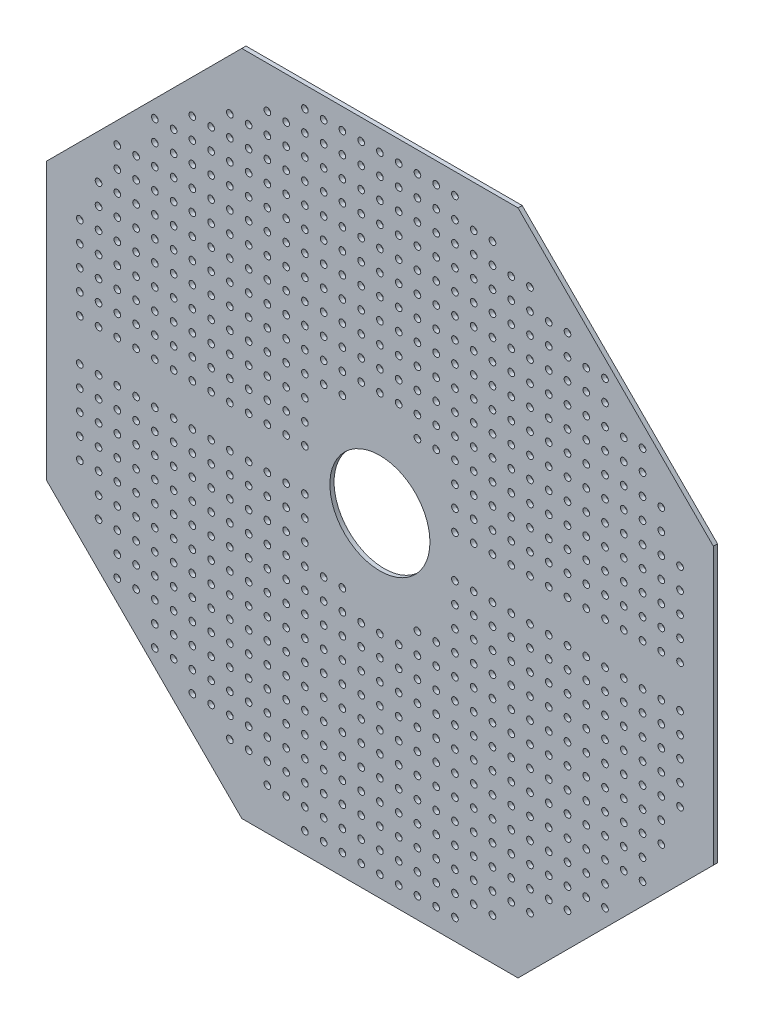
SolidWorks part; units mm, degrees
ref_plane "前视基准面" through (0, 0, 0) normal (0, 0, 1) x (1, 0, 0)
ref_plane "上视基准面" through (0, 0, 0) normal (0, 1, 0) x (1, 0, 0)
ref_plane "右视基准面" through (0, 0, 0) normal (1, 0, 0) x (0, 0, -1)
other "Configuration Table"
sketch "草图1" plane through (0, 0, 0) normal (0, 0, 1) x (1, 0, 0)
  line L0 (-1242.6073, 0) -> (1242.6073, 0) construction
  line L2 (0, -846.9805) -> (0, 846.9805) construction
  line L5 (331.3708, 800) -> (-331.3708, 800)
  line L6 (-331.3708, 800) -> (-800, 331.3708)
  line L7 (-800, 331.3708) -> (-800, -331.3708)
  line L8 (-800, -331.3708) -> (-331.3708, -800)
  line L9 (-331.3708, -800) -> (331.3708, -800)
  line L10 (331.3708, -800) -> (800, -331.3708)
  line L11 (800, -331.3708) -> (800, 331.3708)
  line L12 (800, 331.3708) -> (331.3708, 800)
  circle A2 centre (0, 0) radius 120
  circle A502 centre (0, 0) radius 800 construction
  circle A582 centre (180, 50) radius 8
  circle A583 centre (225, 50) radius 8
  circle A584 centre (270, 50) radius 8
  circle A585 centre (315, 50) radius 8
  circle A586 centre (360, 50) radius 8
  circle A587 centre (405, 50) radius 8
  circle A588 centre (450, 50) radius 8
  circle A589 centre (495, 50) radius 8
  circle A590 centre (540, 50) radius 8
  circle A591 centre (585, 50) radius 8
  circle A592 centre (630, 50) radius 8
  circle A593 centre (675, 50) radius 8
  circle A594 centre (720, 50) radius 8
  circle A599 centre (180, 100) radius 8
  circle A600 centre (225, 100) radius 8
  circle A601 centre (270, 100) radius 8
  circle A602 centre (315, 100) radius 8
  circle A603 centre (360, 100) radius 8
  circle A604 centre (405, 100) radius 8
  circle A605 centre (450, 100) radius 8
  circle A606 centre (495, 100) radius 8
  circle A607 centre (540, 100) radius 8
  circle A608 centre (585, 100) radius 8
  circle A609 centre (630, 100) radius 8
  circle A610 centre (675, 100) radius 8
  circle A611 centre (720, 100) radius 8
  circle A616 centre (180, 150) radius 8
  circle A617 centre (225, 150) radius 8
  circle A618 centre (270, 150) radius 8
  circle A619 centre (315, 150) radius 8
  circle A620 centre (360, 150) radius 8
  circle A621 centre (405, 150) radius 8
  circle A622 centre (450, 150) radius 8
  circle A623 centre (495, 150) radius 8
  circle A624 centre (540, 150) radius 8
  circle A625 centre (585, 150) radius 8
  circle A626 centre (630, 150) radius 8
  circle A627 centre (675, 150) radius 8
  circle A628 centre (720, 150) radius 8
  circle A631 centre (90, 200) radius 8
  circle A632 centre (135, 200) radius 8
  circle A633 centre (180, 200) radius 8
  circle A634 centre (225, 200) radius 8
  circle A635 centre (270, 200) radius 8
  circle A636 centre (315, 200) radius 8
  circle A637 centre (360, 200) radius 8
  circle A638 centre (405, 200) radius 8
  circle A639 centre (450, 200) radius 8
  circle A640 centre (495, 200) radius 8
  circle A641 centre (540, 200) radius 8
  circle A642 centre (585, 200) radius 8
  circle A643 centre (630, 200) radius 8
  circle A644 centre (675, 200) radius 8
  circle A645 centre (720, 200) radius 8
  circle A646 centre (0, 250) radius 8
  circle A647 centre (45, 250) radius 8
  circle A648 centre (90, 250) radius 8
  circle A649 centre (135, 250) radius 8
  circle A650 centre (180, 250) radius 8
  circle A651 centre (225, 250) radius 8
  circle A652 centre (270, 250) radius 8
  circle A653 centre (315, 250) radius 8
  circle A654 centre (360, 250) radius 8
  circle A655 centre (405, 250) radius 8
  circle A656 centre (450, 250) radius 8
  circle A657 centre (495, 250) radius 8
  circle A658 centre (540, 250) radius 8
  circle A659 centre (585, 250) radius 8
  circle A660 centre (630, 250) radius 8
  circle A661 centre (675, 250) radius 8
  circle A662 centre (720, 250) radius 8
  circle A663 centre (0, 300) radius 8
  circle A664 centre (45, 300) radius 8
  circle A665 centre (90, 300) radius 8
  circle A666 centre (135, 300) radius 8
  circle A667 centre (180, 300) radius 8
  circle A668 centre (225, 300) radius 8
  circle A669 centre (270, 300) radius 8
  circle A670 centre (315, 300) radius 8
  circle A671 centre (360, 300) radius 8
  circle A672 centre (405, 300) radius 8
  circle A673 centre (450, 300) radius 8
  circle A674 centre (495, 300) radius 8
  circle A675 centre (540, 300) radius 8
  circle A676 centre (585, 300) radius 8
  circle A677 centre (630, 300) radius 8
  circle A678 centre (675, 300) radius 8
  circle A680 centre (0, 350) radius 8
  circle A681 centre (45, 350) radius 8
  circle A682 centre (90, 350) radius 8
  circle A683 centre (135, 350) radius 8
  circle A684 centre (180, 350) radius 8
  circle A685 centre (225, 350) radius 8
  circle A686 centre (270, 350) radius 8
  circle A687 centre (315, 350) radius 8
  circle A688 centre (360, 350) radius 8
  circle A689 centre (405, 350) radius 8
  circle A690 centre (450, 350) radius 8
  circle A691 centre (495, 350) radius 8
  circle A692 centre (540, 350) radius 8
  circle A693 centre (585, 350) radius 8
  circle A694 centre (630, 350) radius 8
  circle A695 centre (675, 350) radius 8
  circle A697 centre (0, 400) radius 8
  circle A698 centre (45, 400) radius 8
  circle A699 centre (90, 400) radius 8
  circle A700 centre (135, 400) radius 8
  circle A701 centre (180, 400) radius 8
  circle A702 centre (225, 400) radius 8
  circle A703 centre (270, 400) radius 8
  circle A704 centre (315, 400) radius 8
  circle A705 centre (360, 400) radius 8
  circle A706 centre (405, 400) radius 8
  circle A707 centre (450, 400) radius 8
  circle A708 centre (495, 400) radius 8
  circle A709 centre (540, 400) radius 8
  circle A710 centre (585, 400) radius 8
  circle A711 centre (630, 400) radius 8
  circle A714 centre (0, 450) radius 8
  circle A715 centre (45, 450) radius 8
  circle A716 centre (90, 450) radius 8
  circle A717 centre (135, 450) radius 8
  circle A718 centre (180, 450) radius 8
  circle A719 centre (225, 450) radius 8
  circle A720 centre (270, 450) radius 8
  circle A721 centre (315, 450) radius 8
  circle A722 centre (360, 450) radius 8
  circle A723 centre (405, 450) radius 8
  circle A724 centre (450, 450) radius 8
  circle A725 centre (495, 450) radius 8
  circle A726 centre (540, 450) radius 8
  circle A727 centre (585, 450) radius 8
  circle A728 centre (630, 450) radius 8
  circle A731 centre (0, 500) radius 8
  circle A732 centre (45, 500) radius 8
  circle A733 centre (90, 500) radius 8
  circle A734 centre (135, 500) radius 8
  circle A735 centre (180, 500) radius 8
  circle A736 centre (225, 500) radius 8
  circle A737 centre (270, 500) radius 8
  circle A738 centre (315, 500) radius 8
  circle A739 centre (360, 500) radius 8
  circle A740 centre (405, 500) radius 8
  circle A741 centre (450, 500) radius 8
  circle A742 centre (495, 500) radius 8
  circle A743 centre (540, 500) radius 8
  circle A748 centre (0, 550) radius 8
  circle A749 centre (45, 550) radius 8
  circle A750 centre (90, 550) radius 8
  circle A751 centre (135, 550) radius 8
  circle A752 centre (180, 550) radius 8
  circle A753 centre (225, 550) radius 8
  circle A754 centre (270, 550) radius 8
  circle A755 centre (315, 550) radius 8
  circle A756 centre (360, 550) radius 8
  circle A757 centre (405, 550) radius 8
  circle A758 centre (450, 550) radius 8
  circle A759 centre (495, 550) radius 8
  circle A760 centre (540, 550) radius 8
  circle A765 centre (0, 600) radius 8
  circle A766 centre (45, 600) radius 8
  circle A767 centre (90, 600) radius 8
  circle A768 centre (135, 600) radius 8
  circle A769 centre (180, 600) radius 8
  circle A770 centre (225, 600) radius 8
  circle A771 centre (270, 600) radius 8
  circle A772 centre (315, 600) radius 8
  circle A773 centre (360, 600) radius 8
  circle A774 centre (405, 600) radius 8
  circle A775 centre (450, 600) radius 8
  circle A782 centre (0, 650) radius 8
  circle A783 centre (45, 650) radius 8
  circle A784 centre (90, 650) radius 8
  circle A785 centre (135, 650) radius 8
  circle A786 centre (180, 650) radius 8
  circle A787 centre (225, 650) radius 8
  circle A788 centre (270, 650) radius 8
  circle A789 centre (315, 650) radius 8
  circle A790 centre (360, 650) radius 8
  circle A799 centre (0, 700) radius 8
  circle A800 centre (45, 700) radius 8
  circle A801 centre (90, 700) radius 8
  circle A802 centre (135, 700) radius 8
  circle A803 centre (180, 700) radius 8
  circle A804 centre (225, 700) radius 8
  circle A805 centre (270, 700) radius 8
  circle A816 centre (0, 750) radius 8
  circle A817 centre (45, 750) radius 8
  circle A818 centre (90, 750) radius 8
  circle A819 centre (135, 750) radius 8
  circle A820 centre (180, 750) radius 8
  circle A834 centre (-180, 750) radius 8
  circle A835 centre (-135, 750) radius 8
  circle A836 centre (-90, 750) radius 8
  circle A837 centre (-45, 750) radius 8
  circle A838 centre (-270, 700) radius 8
  circle A839 centre (-225, 700) radius 8
  circle A840 centre (-180, 700) radius 8
  circle A841 centre (-135, 700) radius 8
  circle A842 centre (-90, 700) radius 8
  circle A843 centre (-45, 700) radius 8
  circle A844 centre (-360, 650) radius 8
  circle A845 centre (-315, 650) radius 8
  circle A846 centre (-270, 650) radius 8
  circle A847 centre (-225, 650) radius 8
  circle A848 centre (-180, 650) radius 8
  circle A849 centre (-135, 650) radius 8
  circle A850 centre (-90, 650) radius 8
  circle A851 centre (-45, 650) radius 8
  circle A852 centre (-450, 600) radius 8
  circle A853 centre (-405, 600) radius 8
  circle A854 centre (-360, 600) radius 8
  circle A855 centre (-315, 600) radius 8
  circle A856 centre (-270, 600) radius 8
  circle A857 centre (-225, 600) radius 8
  circle A858 centre (-180, 600) radius 8
  circle A859 centre (-135, 600) radius 8
  circle A860 centre (-90, 600) radius 8
  circle A861 centre (-45, 600) radius 8
  circle A862 centre (-540, 550) radius 8
  circle A863 centre (-495, 550) radius 8
  circle A864 centre (-450, 550) radius 8
  circle A865 centre (-405, 550) radius 8
  circle A866 centre (-360, 550) radius 8
  circle A867 centre (-315, 550) radius 8
  circle A868 centre (-270, 550) radius 8
  circle A869 centre (-225, 550) radius 8
  circle A870 centre (-180, 550) radius 8
  circle A871 centre (-135, 550) radius 8
  circle A872 centre (-90, 550) radius 8
  circle A873 centre (-45, 550) radius 8
  circle A874 centre (-540, 500) radius 8
  circle A875 centre (-495, 500) radius 8
  circle A876 centre (-450, 500) radius 8
  circle A877 centre (-405, 500) radius 8
  circle A878 centre (-360, 500) radius 8
  circle A879 centre (-315, 500) radius 8
  circle A880 centre (-270, 500) radius 8
  circle A881 centre (-225, 500) radius 8
  circle A882 centre (-180, 500) radius 8
  circle A883 centre (-135, 500) radius 8
  circle A884 centre (-90, 500) radius 8
  circle A885 centre (-45, 500) radius 8
  circle A886 centre (-630, 450) radius 8
  circle A887 centre (-585, 450) radius 8
  circle A888 centre (-540, 450) radius 8
  circle A889 centre (-495, 450) radius 8
  circle A890 centre (-450, 450) radius 8
  circle A891 centre (-405, 450) radius 8
  circle A892 centre (-360, 450) radius 8
  circle A893 centre (-315, 450) radius 8
  circle A894 centre (-270, 450) radius 8
  circle A895 centre (-225, 450) radius 8
  circle A896 centre (-180, 450) radius 8
  circle A897 centre (-135, 450) radius 8
  circle A898 centre (-90, 450) radius 8
  circle A899 centre (-45, 450) radius 8
  circle A900 centre (-630, 400) radius 8
  circle A901 centre (-585, 400) radius 8
  circle A902 centre (-540, 400) radius 8
  circle A903 centre (-495, 400) radius 8
  circle A904 centre (-450, 400) radius 8
  circle A905 centre (-405, 400) radius 8
  circle A906 centre (-360, 400) radius 8
  circle A907 centre (-315, 400) radius 8
  circle A908 centre (-270, 400) radius 8
  circle A909 centre (-225, 400) radius 8
  circle A910 centre (-180, 400) radius 8
  circle A911 centre (-135, 400) radius 8
  circle A912 centre (-90, 400) radius 8
  circle A913 centre (-45, 400) radius 8
  circle A914 centre (-675, 350) radius 8
  circle A915 centre (-630, 350) radius 8
  circle A916 centre (-585, 350) radius 8
  circle A917 centre (-540, 350) radius 8
  circle A918 centre (-495, 350) radius 8
  circle A919 centre (-450, 350) radius 8
  circle A920 centre (-405, 350) radius 8
  circle A921 centre (-360, 350) radius 8
  circle A922 centre (-315, 350) radius 8
  circle A923 centre (-270, 350) radius 8
  circle A924 centre (-225, 350) radius 8
  circle A925 centre (-180, 350) radius 8
  circle A926 centre (-135, 350) radius 8
  circle A927 centre (-90, 350) radius 8
  circle A928 centre (-45, 350) radius 8
  circle A929 centre (-675, 300) radius 8
  circle A930 centre (-630, 300) radius 8
  circle A931 centre (-585, 300) radius 8
  circle A932 centre (-540, 300) radius 8
  circle A933 centre (-495, 300) radius 8
  circle A934 centre (-450, 300) radius 8
  circle A935 centre (-405, 300) radius 8
  circle A936 centre (-360, 300) radius 8
  circle A937 centre (-315, 300) radius 8
  circle A938 centre (-270, 300) radius 8
  circle A939 centre (-225, 300) radius 8
  circle A940 centre (-180, 300) radius 8
  circle A941 centre (-135, 300) radius 8
  circle A942 centre (-90, 300) radius 8
  circle A943 centre (-45, 300) radius 8
  circle A944 centre (-720, 250) radius 8
  circle A945 centre (-675, 250) radius 8
  circle A946 centre (-630, 250) radius 8
  circle A947 centre (-585, 250) radius 8
  circle A948 centre (-540, 250) radius 8
  circle A949 centre (-495, 250) radius 8
  circle A950 centre (-450, 250) radius 8
  circle A951 centre (-405, 250) radius 8
  circle A952 centre (-360, 250) radius 8
  circle A953 centre (-315, 250) radius 8
  circle A954 centre (-270, 250) radius 8
  circle A955 centre (-225, 250) radius 8
  circle A956 centre (-180, 250) radius 8
  circle A957 centre (-135, 250) radius 8
  circle A958 centre (-90, 250) radius 8
  circle A959 centre (-45, 250) radius 8
  circle A960 centre (-720, 200) radius 8
  circle A961 centre (-675, 200) radius 8
  circle A962 centre (-630, 200) radius 8
  circle A963 centre (-585, 200) radius 8
  circle A964 centre (-540, 200) radius 8
  circle A965 centre (-495, 200) radius 8
  circle A966 centre (-450, 200) radius 8
  circle A967 centre (-405, 200) radius 8
  circle A968 centre (-360, 200) radius 8
  circle A969 centre (-315, 200) radius 8
  circle A970 centre (-270, 200) radius 8
  circle A971 centre (-225, 200) radius 8
  circle A972 centre (-180, 200) radius 8
  circle A973 centre (-135, 200) radius 8
  circle A974 centre (-90, 200) radius 8
  circle A975 centre (-720, 150) radius 8
  circle A976 centre (-675, 150) radius 8
  circle A977 centre (-630, 150) radius 8
  circle A978 centre (-585, 150) radius 8
  circle A979 centre (-540, 150) radius 8
  circle A980 centre (-495, 150) radius 8
  circle A981 centre (-450, 150) radius 8
  circle A982 centre (-405, 150) radius 8
  circle A983 centre (-360, 150) radius 8
  circle A984 centre (-315, 150) radius 8
  circle A985 centre (-270, 150) radius 8
  circle A986 centre (-225, 150) radius 8
  circle A987 centre (-180, 150) radius 8
  circle A988 centre (-720, 100) radius 8
  circle A989 centre (-675, 100) radius 8
  circle A990 centre (-630, 100) radius 8
  circle A991 centre (-585, 100) radius 8
  circle A992 centre (-540, 100) radius 8
  circle A993 centre (-495, 100) radius 8
  circle A994 centre (-450, 100) radius 8
  circle A995 centre (-405, 100) radius 8
  circle A996 centre (-360, 100) radius 8
  circle A997 centre (-315, 100) radius 8
  circle A998 centre (-270, 100) radius 8
  circle A999 centre (-225, 100) radius 8
  circle A1000 centre (-180, 100) radius 8
  circle A1001 centre (-720, 50) radius 8
  circle A1002 centre (-675, 50) radius 8
  circle A1003 centre (-630, 50) radius 8
  circle A1004 centre (-585, 50) radius 8
  circle A1005 centre (-540, 50) radius 8
  circle A1006 centre (-495, 50) radius 8
  circle A1007 centre (-450, 50) radius 8
  circle A1008 centre (-405, 50) radius 8
  circle A1009 centre (-360, 50) radius 8
  circle A1010 centre (-315, 50) radius 8
  circle A1011 centre (-270, 50) radius 8
  circle A1012 centre (-225, 50) radius 8
  circle A1013 centre (-180, 50) radius 8
  circle A1014 centre (-180, -50) radius 8
  circle A1015 centre (-225, -50) radius 8
  circle A1016 centre (-270, -50) radius 8
  circle A1017 centre (-315, -50) radius 8
  circle A1018 centre (-360, -50) radius 8
  circle A1019 centre (-405, -50) radius 8
  circle A1020 centre (-450, -50) radius 8
  circle A1021 centre (-495, -50) radius 8
  circle A1022 centre (-540, -50) radius 8
  circle A1023 centre (-585, -50) radius 8
  circle A1024 centre (-630, -50) radius 8
  circle A1025 centre (-675, -50) radius 8
  circle A1026 centre (-720, -50) radius 8
  circle A1027 centre (-180, -100) radius 8
  circle A1028 centre (-225, -100) radius 8
  circle A1029 centre (-270, -100) radius 8
  circle A1030 centre (-315, -100) radius 8
  circle A1031 centre (-360, -100) radius 8
  circle A1032 centre (-405, -100) radius 8
  circle A1033 centre (-450, -100) radius 8
  circle A1034 centre (-495, -100) radius 8
  circle A1035 centre (-540, -100) radius 8
  circle A1036 centre (-585, -100) radius 8
  circle A1037 centre (-630, -100) radius 8
  circle A1038 centre (-675, -100) radius 8
  circle A1039 centre (-720, -100) radius 8
  circle A1040 centre (-180, -150) radius 8
  circle A1041 centre (-225, -150) radius 8
  circle A1042 centre (-270, -150) radius 8
  circle A1043 centre (-315, -150) radius 8
  circle A1044 centre (-360, -150) radius 8
  circle A1045 centre (-405, -150) radius 8
  circle A1046 centre (-450, -150) radius 8
  circle A1047 centre (-495, -150) radius 8
  circle A1048 centre (-540, -150) radius 8
  circle A1049 centre (-585, -150) radius 8
  circle A1050 centre (-630, -150) radius 8
  circle A1051 centre (-675, -150) radius 8
  circle A1052 centre (-720, -150) radius 8
  circle A1053 centre (-90, -200) radius 8
  circle A1054 centre (-135, -200) radius 8
  circle A1055 centre (-180, -200) radius 8
  circle A1056 centre (-225, -200) radius 8
  circle A1057 centre (-270, -200) radius 8
  circle A1058 centre (-315, -200) radius 8
  circle A1059 centre (-360, -200) radius 8
  circle A1060 centre (-405, -200) radius 8
  circle A1061 centre (-450, -200) radius 8
  circle A1062 centre (-495, -200) radius 8
  circle A1063 centre (-540, -200) radius 8
  circle A1064 centre (-585, -200) radius 8
  circle A1065 centre (-630, -200) radius 8
  circle A1066 centre (-675, -200) radius 8
  circle A1067 centre (-720, -200) radius 8
  circle A1068 centre (-45, -250) radius 8
  circle A1069 centre (-90, -250) radius 8
  circle A1070 centre (-135, -250) radius 8
  circle A1071 centre (-180, -250) radius 8
  circle A1072 centre (-225, -250) radius 8
  circle A1073 centre (-270, -250) radius 8
  circle A1074 centre (-315, -250) radius 8
  circle A1075 centre (-360, -250) radius 8
  circle A1076 centre (-405, -250) radius 8
  circle A1077 centre (-450, -250) radius 8
  circle A1078 centre (-495, -250) radius 8
  circle A1079 centre (-540, -250) radius 8
  circle A1080 centre (-585, -250) radius 8
  circle A1081 centre (-630, -250) radius 8
  circle A1082 centre (-675, -250) radius 8
  circle A1083 centre (-720, -250) radius 8
  circle A1084 centre (-45, -300) radius 8
  circle A1085 centre (-90, -300) radius 8
  circle A1086 centre (-135, -300) radius 8
  circle A1087 centre (-180, -300) radius 8
  circle A1088 centre (-225, -300) radius 8
  circle A1089 centre (-270, -300) radius 8
  circle A1090 centre (-315, -300) radius 8
  circle A1091 centre (-360, -300) radius 8
  circle A1092 centre (-405, -300) radius 8
  circle A1093 centre (-450, -300) radius 8
  circle A1094 centre (-495, -300) radius 8
  circle A1095 centre (-540, -300) radius 8
  circle A1096 centre (-585, -300) radius 8
  circle A1097 centre (-630, -300) radius 8
  circle A1098 centre (-675, -300) radius 8
  circle A1099 centre (-45, -350) radius 8
  circle A1100 centre (-90, -350) radius 8
  circle A1101 centre (-135, -350) radius 8
  circle A1102 centre (-180, -350) radius 8
  circle A1103 centre (-225, -350) radius 8
  circle A1104 centre (-270, -350) radius 8
  circle A1105 centre (-315, -350) radius 8
  circle A1106 centre (-360, -350) radius 8
  circle A1107 centre (-405, -350) radius 8
  circle A1108 centre (-450, -350) radius 8
  circle A1109 centre (-495, -350) radius 8
  circle A1110 centre (-540, -350) radius 8
  circle A1111 centre (-585, -350) radius 8
  circle A1112 centre (-630, -350) radius 8
  circle A1113 centre (-675, -350) radius 8
  circle A1114 centre (-45, -400) radius 8
  circle A1115 centre (-90, -400) radius 8
  circle A1116 centre (-135, -400) radius 8
  circle A1117 centre (-180, -400) radius 8
  circle A1118 centre (-225, -400) radius 8
  circle A1119 centre (-270, -400) radius 8
  circle A1120 centre (-315, -400) radius 8
  circle A1121 centre (-360, -400) radius 8
  circle A1122 centre (-405, -400) radius 8
  circle A1123 centre (-450, -400) radius 8
  circle A1124 centre (-495, -400) radius 8
  circle A1125 centre (-540, -400) radius 8
  circle A1126 centre (-585, -400) radius 8
  circle A1127 centre (-630, -400) radius 8
  circle A1128 centre (-45, -450) radius 8
  circle A1129 centre (-90, -450) radius 8
  circle A1130 centre (-135, -450) radius 8
  circle A1131 centre (-180, -450) radius 8
  circle A1132 centre (-225, -450) radius 8
  circle A1133 centre (-270, -450) radius 8
  circle A1134 centre (-315, -450) radius 8
  circle A1135 centre (-360, -450) radius 8
  circle A1136 centre (-405, -450) radius 8
  circle A1137 centre (-450, -450) radius 8
  circle A1138 centre (-495, -450) radius 8
  circle A1139 centre (-540, -450) radius 8
  circle A1140 centre (-585, -450) radius 8
  circle A1141 centre (-630, -450) radius 8
  circle A1142 centre (-45, -500) radius 8
  circle A1143 centre (-90, -500) radius 8
  circle A1144 centre (-135, -500) radius 8
  circle A1145 centre (-180, -500) radius 8
  circle A1146 centre (-225, -500) radius 8
  circle A1147 centre (-270, -500) radius 8
  circle A1148 centre (-315, -500) radius 8
  circle A1149 centre (-360, -500) radius 8
  circle A1150 centre (-405, -500) radius 8
  circle A1151 centre (-450, -500) radius 8
  circle A1152 centre (-495, -500) radius 8
  circle A1153 centre (-540, -500) radius 8
  circle A1154 centre (-45, -550) radius 8
  circle A1155 centre (-90, -550) radius 8
  circle A1156 centre (-135, -550) radius 8
  circle A1157 centre (-180, -550) radius 8
  circle A1158 centre (-225, -550) radius 8
  circle A1159 centre (-270, -550) radius 8
  circle A1160 centre (-315, -550) radius 8
  circle A1161 centre (-360, -550) radius 8
  circle A1162 centre (-405, -550) radius 8
  circle A1163 centre (-450, -550) radius 8
  circle A1164 centre (-495, -550) radius 8
  circle A1165 centre (-540, -550) radius 8
  circle A1166 centre (-45, -600) radius 8
  circle A1167 centre (-90, -600) radius 8
  circle A1168 centre (-135, -600) radius 8
  circle A1169 centre (-180, -600) radius 8
  circle A1170 centre (-225, -600) radius 8
  circle A1171 centre (-270, -600) radius 8
  circle A1172 centre (-315, -600) radius 8
  circle A1173 centre (-360, -600) radius 8
  circle A1174 centre (-405, -600) radius 8
  circle A1175 centre (-450, -600) radius 8
  circle A1176 centre (-45, -650) radius 8
  circle A1177 centre (-90, -650) radius 8
  circle A1178 centre (-135, -650) radius 8
  circle A1179 centre (-180, -650) radius 8
  circle A1180 centre (-225, -650) radius 8
  circle A1181 centre (-270, -650) radius 8
  circle A1182 centre (-315, -650) radius 8
  circle A1183 centre (-360, -650) radius 8
  circle A1184 centre (-45, -700) radius 8
  circle A1185 centre (-90, -700) radius 8
  circle A1186 centre (-135, -700) radius 8
  circle A1187 centre (-180, -700) radius 8
  circle A1188 centre (-225, -700) radius 8
  circle A1189 centre (-270, -700) radius 8
  circle A1190 centre (-45, -750) radius 8
  circle A1191 centre (-90, -750) radius 8
  circle A1192 centre (-135, -750) radius 8
  circle A1193 centre (-180, -750) radius 8
  circle A1194 centre (180, -750) radius 8
  circle A1195 centre (135, -750) radius 8
  circle A1196 centre (90, -750) radius 8
  circle A1197 centre (45, -750) radius 8
  circle A1198 centre (0, -750) radius 8
  circle A1199 centre (270, -700) radius 8
  circle A1200 centre (225, -700) radius 8
  circle A1201 centre (180, -700) radius 8
  circle A1202 centre (135, -700) radius 8
  circle A1203 centre (90, -700) radius 8
  circle A1204 centre (45, -700) radius 8
  circle A1205 centre (0, -700) radius 8
  circle A1206 centre (360, -650) radius 8
  circle A1207 centre (315, -650) radius 8
  circle A1208 centre (270, -650) radius 8
  circle A1209 centre (225, -650) radius 8
  circle A1210 centre (180, -650) radius 8
  circle A1211 centre (135, -650) radius 8
  circle A1212 centre (90, -650) radius 8
  circle A1213 centre (45, -650) radius 8
  circle A1214 centre (0, -650) radius 8
  circle A1215 centre (450, -600) radius 8
  circle A1216 centre (405, -600) radius 8
  circle A1217 centre (360, -600) radius 8
  circle A1218 centre (315, -600) radius 8
  circle A1219 centre (270, -600) radius 8
  circle A1220 centre (225, -600) radius 8
  circle A1221 centre (180, -600) radius 8
  circle A1222 centre (135, -600) radius 8
  circle A1223 centre (90, -600) radius 8
  circle A1224 centre (45, -600) radius 8
  circle A1225 centre (0, -600) radius 8
  circle A1226 centre (540, -550) radius 8
  circle A1227 centre (495, -550) radius 8
  circle A1228 centre (450, -550) radius 8
  circle A1229 centre (405, -550) radius 8
  circle A1230 centre (360, -550) radius 8
  circle A1231 centre (315, -550) radius 8
  circle A1232 centre (270, -550) radius 8
  circle A1233 centre (225, -550) radius 8
  circle A1234 centre (180, -550) radius 8
  circle A1235 centre (135, -550) radius 8
  circle A1236 centre (90, -550) radius 8
  circle A1237 centre (45, -550) radius 8
  circle A1238 centre (0, -550) radius 8
  circle A1239 centre (540, -500) radius 8
  circle A1240 centre (495, -500) radius 8
  circle A1241 centre (450, -500) radius 8
  circle A1242 centre (405, -500) radius 8
  circle A1243 centre (360, -500) radius 8
  circle A1244 centre (315, -500) radius 8
  circle A1245 centre (270, -500) radius 8
  circle A1246 centre (225, -500) radius 8
  circle A1247 centre (180, -500) radius 8
  circle A1248 centre (135, -500) radius 8
  circle A1249 centre (90, -500) radius 8
  circle A1250 centre (45, -500) radius 8
  circle A1251 centre (0, -500) radius 8
  circle A1252 centre (630, -450) radius 8
  circle A1253 centre (585, -450) radius 8
  circle A1254 centre (540, -450) radius 8
  circle A1255 centre (495, -450) radius 8
  circle A1256 centre (450, -450) radius 8
  circle A1257 centre (405, -450) radius 8
  circle A1258 centre (360, -450) radius 8
  circle A1259 centre (315, -450) radius 8
  circle A1260 centre (270, -450) radius 8
  circle A1261 centre (225, -450) radius 8
  circle A1262 centre (180, -450) radius 8
  circle A1263 centre (135, -450) radius 8
  circle A1264 centre (90, -450) radius 8
  circle A1265 centre (45, -450) radius 8
  circle A1266 centre (0, -450) radius 8
  circle A1267 centre (630, -400) radius 8
  circle A1268 centre (585, -400) radius 8
  circle A1269 centre (540, -400) radius 8
  circle A1270 centre (495, -400) radius 8
  circle A1271 centre (450, -400) radius 8
  circle A1272 centre (405, -400) radius 8
  circle A1273 centre (360, -400) radius 8
  circle A1274 centre (315, -400) radius 8
  circle A1275 centre (270, -400) radius 8
  circle A1276 centre (225, -400) radius 8
  circle A1277 centre (180, -400) radius 8
  circle A1278 centre (135, -400) radius 8
  circle A1279 centre (90, -400) radius 8
  circle A1280 centre (45, -400) radius 8
  circle A1281 centre (0, -400) radius 8
  circle A1282 centre (675, -350) radius 8
  circle A1283 centre (630, -350) radius 8
  circle A1284 centre (585, -350) radius 8
  circle A1285 centre (540, -350) radius 8
  circle A1286 centre (495, -350) radius 8
  circle A1287 centre (450, -350) radius 8
  circle A1288 centre (405, -350) radius 8
  circle A1289 centre (360, -350) radius 8
  circle A1290 centre (315, -350) radius 8
  circle A1291 centre (270, -350) radius 8
  circle A1292 centre (225, -350) radius 8
  circle A1293 centre (180, -350) radius 8
  circle A1294 centre (135, -350) radius 8
  circle A1295 centre (90, -350) radius 8
  circle A1296 centre (45, -350) radius 8
  circle A1297 centre (0, -350) radius 8
  circle A1298 centre (675, -300) radius 8
  circle A1299 centre (630, -300) radius 8
  circle A1300 centre (585, -300) radius 8
  circle A1301 centre (540, -300) radius 8
  circle A1302 centre (495, -300) radius 8
  circle A1303 centre (450, -300) radius 8
  circle A1304 centre (405, -300) radius 8
  circle A1305 centre (360, -300) radius 8
  circle A1306 centre (315, -300) radius 8
  circle A1307 centre (270, -300) radius 8
  circle A1308 centre (225, -300) radius 8
  circle A1309 centre (180, -300) radius 8
  circle A1310 centre (135, -300) radius 8
  circle A1311 centre (90, -300) radius 8
  circle A1312 centre (45, -300) radius 8
  circle A1313 centre (0, -300) radius 8
  circle A1314 centre (720, -250) radius 8
  circle A1315 centre (675, -250) radius 8
  circle A1316 centre (630, -250) radius 8
  circle A1317 centre (585, -250) radius 8
  circle A1318 centre (540, -250) radius 8
  circle A1319 centre (495, -250) radius 8
  circle A1320 centre (450, -250) radius 8
  circle A1321 centre (405, -250) radius 8
  circle A1322 centre (360, -250) radius 8
  circle A1323 centre (315, -250) radius 8
  circle A1324 centre (270, -250) radius 8
  circle A1325 centre (225, -250) radius 8
  circle A1326 centre (180, -250) radius 8
  circle A1327 centre (135, -250) radius 8
  circle A1328 centre (90, -250) radius 8
  circle A1329 centre (45, -250) radius 8
  circle A1330 centre (0, -250) radius 8
  circle A1331 centre (720, -200) radius 8
  circle A1332 centre (675, -200) radius 8
  circle A1333 centre (630, -200) radius 8
  circle A1334 centre (585, -200) radius 8
  circle A1335 centre (540, -200) radius 8
  circle A1336 centre (495, -200) radius 8
  circle A1337 centre (450, -200) radius 8
  circle A1338 centre (405, -200) radius 8
  circle A1339 centre (360, -200) radius 8
  circle A1340 centre (315, -200) radius 8
  circle A1341 centre (270, -200) radius 8
  circle A1342 centre (225, -200) radius 8
  circle A1343 centre (180, -200) radius 8
  circle A1344 centre (135, -200) radius 8
  circle A1345 centre (90, -200) radius 8
  circle A1346 centre (720, -150) radius 8
  circle A1347 centre (675, -150) radius 8
  circle A1348 centre (630, -150) radius 8
  circle A1349 centre (585, -150) radius 8
  circle A1350 centre (540, -150) radius 8
  circle A1351 centre (495, -150) radius 8
  circle A1352 centre (450, -150) radius 8
  circle A1353 centre (405, -150) radius 8
  circle A1354 centre (360, -150) radius 8
  circle A1355 centre (315, -150) radius 8
  circle A1356 centre (270, -150) radius 8
  circle A1357 centre (225, -150) radius 8
  circle A1358 centre (180, -150) radius 8
  circle A1359 centre (720, -100) radius 8
  circle A1360 centre (675, -100) radius 8
  circle A1361 centre (630, -100) radius 8
  circle A1362 centre (585, -100) radius 8
  circle A1363 centre (540, -100) radius 8
  circle A1364 centre (495, -100) radius 8
  circle A1365 centre (450, -100) radius 8
  circle A1366 centre (405, -100) radius 8
  circle A1367 centre (360, -100) radius 8
  circle A1368 centre (315, -100) radius 8
  circle A1369 centre (270, -100) radius 8
  circle A1370 centre (225, -100) radius 8
  circle A1371 centre (180, -100) radius 8
  circle A1372 centre (720, -50) radius 8
  circle A1373 centre (675, -50) radius 8
  circle A1374 centre (630, -50) radius 8
  circle A1375 centre (585, -50) radius 8
  circle A1376 centre (540, -50) radius 8
  circle A1377 centre (495, -50) radius 8
  circle A1378 centre (450, -50) radius 8
  circle A1379 centre (405, -50) radius 8
  circle A1380 centre (360, -50) radius 8
  circle A1381 centre (315, -50) radius 8
  circle A1382 centre (270, -50) radius 8
  circle A1383 centre (225, -50) radius 8
  circle A1384 centre (180, -50) radius 8
  dimension "D2" = 240
extrude "凸台-拉伸1" add sketch "草图1" along normal blind 10
sketch "草图2" plane through (0, 0, 0) normal (0, 0, 1) x (1, 0, 0)
  line L0 (-1217.1484, 0) -> (1217.1484, 0) construction
  line L1 (0, 936.9576) -> (0, -936.9576) construction
  line L18 (-217, 42) -> (-217, 408)
  line L19 (-217, 42) -> (-278, 42)
  line L20 (-278, 42) -> (-278, 408)
  line L21 (-217, 408) -> (-278, 408)
  line L22 (-307, 42) -> (-307, 408)
  line L23 (-307, 42) -> (-368, 42)
  line L24 (-368, 42) -> (-368, 408)
  line L25 (-307, 408) -> (-368, 408)
  line L26 (-397, 242) -> (-397, 608)
  line L27 (-397, 242) -> (-458, 242)
  line L28 (-458, 242) -> (-458, 608)
  line L29 (-397, 608) -> (-458, 608)
  line L30 (-487, 242) -> (-487, 608)
  line L31 (-487, 242) -> (-548, 242)
  line L32 (-548, 242) -> (-548, 608)
  line L33 (-487, 608) -> (-548, 608)
  line L34 (-577, 142) -> (-577, 508)
  line L35 (-577, 142) -> (-638, 142)
  line L36 (-638, 142) -> (-638, 508)
  line L37 (-577, 508) -> (-638, 508)
  line L38 (-667, 42) -> (-667, 408)
  line L39 (-667, 42) -> (-728, 42)
  line L40 (-728, 42) -> (-728, 408)
  line L41 (-667, 408) -> (-728, 408)
  line L42 (-307, 442) -> (-307, 808)
  line L43 (-307, 442) -> (-368, 442)
  line L44 (-368, 442) -> (-368, 808)
  line L45 (-307, 808) -> (-368, 808)
  line L46 (-217, 442) -> (-217, 808)
  line L47 (-217, 442) -> (-278, 442)
  line L48 (-278, 442) -> (-278, 808)
  line L49 (-217, 808) -> (-278, 808)
  line L50 (-127, 442) -> (-127, 808)
  line L51 (-127, 442) -> (-188, 442)
  line L52 (-188, 442) -> (-188, 808)
  line L53 (-127, 808) -> (-188, 808)
  line L54 (-37, 192) -> (-37, 558)
  line L55 (-98, 192) -> (-98, 558)
  line L56 (-37, 558) -> (-98, 558)
  line L57 (-37, 192) -> (-98, 192)
  line L58 (53, 192) -> (53, 558)
  line L59 (-8, 192) -> (-8, 558)
  line L60 (53, 558) -> (-8, 558)
  line L61 (53, 192) -> (-8, 192)
  line L62 (143, 192) -> (143, 558)
  line L63 (82, 192) -> (82, 558)
  line L64 (143, 558) -> (82, 558)
  line L65 (143, 192) -> (82, 192)
  line L66 (233, 42) -> (233, 408)
  line L67 (172, 42) -> (172, 408)
  line L68 (233, 408) -> (172, 408)
  line L69 (233, 42) -> (172, 42)
  line L70 (323, 42) -> (323, 408)
  line L71 (262, 42) -> (262, 408)
  line L72 (323, 408) -> (262, 408)
  line L73 (323, 42) -> (262, 42)
  line L74 (413, 42) -> (413, 408)
  line L75 (352, 42) -> (352, 408)
  line L76 (413, 408) -> (352, 408)
  line L77 (413, 42) -> (352, 42)
  line L78 (503, 42) -> (503, 408)
  line L79 (442, 42) -> (442, 408)
  line L80 (503, 408) -> (442, 408)
  line L81 (503, 42) -> (442, 42)
  line L82 (593, 42) -> (593, 408)
  line L83 (532, 42) -> (532, 408)
  line L84 (593, 408) -> (532, 408)
  line L85 (593, 42) -> (532, 42)
  line L86 (683, 508) -> (622, 508)
  line L87 (622, 142) -> (622, 508)
  line L88 (683, 142) -> (622, 142)
  line L89 (683, 142) -> (683, 508)
  line L90 (773, 408) -> (712, 408)
  line L91 (712, 42) -> (712, 408)
  line L92 (773, 42) -> (712, 42)
  line L93 (773, 42) -> (773, 408)
  line L94 (233, 808) -> (172, 808)
  line L95 (172, 442) -> (172, 808)
  line L96 (233, 442) -> (172, 442)
  line L97 (233, 442) -> (233, 808)
  line L98 (323, 808) -> (262, 808)
  line L99 (262, 442) -> (262, 808)
  line L100 (323, 442) -> (262, 442)
  line L101 (323, 442) -> (323, 808)
  line L102 (413, 808) -> (352, 808)
  line L103 (352, 442) -> (352, 808)
  line L104 (413, 442) -> (352, 442)
  line L105 (413, 442) -> (413, 808)
  line L106 (-458, 208) -> (-458, 42)
  line L107 (-548, 208) -> (-487, 208)
  line L108 (-548, 208) -> (-548, 42)
  line L109 (-548, 42) -> (-487, 42)
  line L110 (-487, 208) -> (-487, 42)
  line L111 (-397, 208) -> (-397, 42)
  line L112 (-458, 42) -> (-397, 42)
  line L113 (-458, 208) -> (-397, 208)
  line L114 (-98, 758) -> (-98, 592)
  line L115 (-37, 758) -> (-37, 592)
  line L116 (-98, 592) -> (-37, 592)
  line L117 (-98, 758) -> (-37, 758)
  line L118 (-8, 758) -> (-8, 592)
  line L119 (53, 758) -> (53, 592)
  line L120 (-8, 592) -> (53, 592)
  line L121 (-8, 758) -> (53, 758)
  line L122 (82, 758) -> (82, 592)
  line L123 (143, 758) -> (143, 592)
  line L124 (82, 592) -> (143, 592)
  line L125 (82, 758) -> (143, 758)
  line L126 (442, 608) -> (442, 442)
  line L127 (503, 608) -> (503, 442)
  line L128 (442, 442) -> (503, 442)
  line L129 (442, 608) -> (503, 608)
  line L130 (532, 608) -> (532, 442)
  line L131 (593, 608) -> (593, 442)
  line L132 (532, 442) -> (593, 442)
  line L133 (532, 608) -> (593, 608)
  line L134 (532, -608) -> (593, -608)
  line L135 (532, -442) -> (593, -442)
  line L136 (593, -608) -> (593, -442)
  line L137 (532, -608) -> (532, -442)
  line L138 (442, -608) -> (503, -608)
  line L139 (442, -442) -> (503, -442)
  line L140 (503, -608) -> (503, -442)
  line L141 (442, -608) -> (442, -442)
  line L142 (82, -758) -> (143, -758)
  line L143 (82, -592) -> (143, -592)
  line L144 (143, -758) -> (143, -592)
  line L145 (82, -758) -> (82, -592)
  line L146 (-8, -758) -> (53, -758)
  line L147 (-8, -592) -> (53, -592)
  line L148 (53, -758) -> (53, -592)
  line L149 (-8, -758) -> (-8, -592)
  line L150 (-98, -758) -> (-37, -758)
  line L151 (-98, -592) -> (-37, -592)
  line L152 (-37, -758) -> (-37, -592)
  line L153 (-98, -758) -> (-98, -592)
  line L154 (-458, -208) -> (-397, -208)
  line L155 (-458, -42) -> (-397, -42)
  line L156 (-397, -208) -> (-397, -42)
  line L157 (-487, -208) -> (-487, -42)
  line L158 (-548, -42) -> (-487, -42)
  line L159 (-548, -208) -> (-548, -42)
  line L160 (-548, -208) -> (-487, -208)
  line L161 (-458, -208) -> (-458, -42)
  line L162 (413, -442) -> (413, -808)
  line L163 (413, -442) -> (352, -442)
  line L164 (352, -442) -> (352, -808)
  line L165 (413, -808) -> (352, -808)
  line L166 (323, -442) -> (323, -808)
  line L167 (323, -442) -> (262, -442)
  line L168 (262, -442) -> (262, -808)
  line L169 (323, -808) -> (262, -808)
  line L170 (233, -442) -> (233, -808)
  line L171 (233, -442) -> (172, -442)
  line L172 (172, -442) -> (172, -808)
  line L173 (233, -808) -> (172, -808)
  line L174 (773, -42) -> (773, -408)
  line L175 (773, -42) -> (712, -42)
  line L176 (712, -42) -> (712, -408)
  line L177 (773, -408) -> (712, -408)
  line L178 (683, -142) -> (683, -508)
  line L179 (683, -142) -> (622, -142)
  line L180 (622, -142) -> (622, -508)
  line L181 (683, -508) -> (622, -508)
  line L182 (593, -42) -> (532, -42)
  line L183 (593, -408) -> (532, -408)
  line L184 (532, -42) -> (532, -408)
  line L185 (593, -42) -> (593, -408)
  line L186 (503, -42) -> (442, -42)
  line L187 (503, -408) -> (442, -408)
  line L188 (442, -42) -> (442, -408)
  line L189 (503, -42) -> (503, -408)
  line L190 (413, -42) -> (352, -42)
  line L191 (413, -408) -> (352, -408)
  line L192 (352, -42) -> (352, -408)
  line L193 (413, -42) -> (413, -408)
  line L194 (323, -42) -> (262, -42)
  line L195 (323, -408) -> (262, -408)
  line L196 (262, -42) -> (262, -408)
  line L197 (323, -42) -> (323, -408)
  line L198 (233, -42) -> (172, -42)
  line L199 (233, -408) -> (172, -408)
  line L200 (172, -42) -> (172, -408)
  line L201 (233, -42) -> (233, -408)
  line L202 (143, -192) -> (82, -192)
  line L203 (143, -558) -> (82, -558)
  line L204 (82, -192) -> (82, -558)
  line L205 (143, -192) -> (143, -558)
  line L206 (53, -192) -> (-8, -192)
  line L207 (53, -558) -> (-8, -558)
  line L208 (-8, -192) -> (-8, -558)
  line L209 (53, -192) -> (53, -558)
  line L210 (-37, -192) -> (-98, -192)
  line L211 (-37, -558) -> (-98, -558)
  line L212 (-98, -192) -> (-98, -558)
  line L213 (-37, -192) -> (-37, -558)
  line L214 (-127, -808) -> (-188, -808)
  line L215 (-188, -442) -> (-188, -808)
  line L216 (-127, -442) -> (-188, -442)
  line L217 (-127, -442) -> (-127, -808)
  line L218 (-217, -808) -> (-278, -808)
  line L219 (-278, -442) -> (-278, -808)
  line L220 (-217, -442) -> (-278, -442)
  line L221 (-217, -442) -> (-217, -808)
  line L222 (-307, -808) -> (-368, -808)
  line L223 (-368, -442) -> (-368, -808)
  line L224 (-307, -442) -> (-368, -442)
  line L225 (-307, -442) -> (-307, -808)
  line L226 (-667, -408) -> (-728, -408)
  line L227 (-728, -42) -> (-728, -408)
  line L228 (-667, -42) -> (-728, -42)
  line L229 (-667, -42) -> (-667, -408)
  line L230 (-577, -508) -> (-638, -508)
  line L231 (-638, -142) -> (-638, -508)
  line L232 (-577, -142) -> (-638, -142)
  line L233 (-577, -142) -> (-577, -508)
  line L234 (-487, -608) -> (-548, -608)
  line L235 (-548, -242) -> (-548, -608)
  line L236 (-487, -242) -> (-548, -242)
  line L237 (-487, -242) -> (-487, -608)
  line L238 (-397, -608) -> (-458, -608)
  line L239 (-458, -242) -> (-458, -608)
  line L240 (-397, -242) -> (-458, -242)
  line L241 (-397, -242) -> (-397, -608)
  line L242 (-307, -408) -> (-368, -408)
  line L243 (-368, -42) -> (-368, -408)
  line L244 (-307, -42) -> (-368, -42)
  line L245 (-307, -42) -> (-307, -408)
  line L246 (-217, -408) -> (-278, -408)
  line L247 (-278, -42) -> (-278, -408)
  line L248 (-217, -42) -> (-278, -42)
  line L249 (-217, -42) -> (-217, -408)
  line L250 (-127, -42) -> (-188, -42)
  line L251 (-127, -42) -> (-127, -408)
  line L252 (-188, -42) -> (-188, -408)
  line L253 (-127, -408) -> (-188, -408)
  line L254 (-188, 42) -> (-188, 408)
  line L255 (-638, 111.8983) -> (-577, 111.8983)
  line L256 (-638, 111.8983) -> (-638, -108)
  line L257 (-638, -108) -> (-577, -108)
  line L258 (-577, 111.8983) -> (-577, -108)
  line L259 (622, 108) -> (683, 108)
  line L260 (622, 108) -> (622, -108)
  line L261 (622, -108) -> (683, -108)
  line L262 (683, 108) -> (683, -108)
  line L263 (-127, 408) -> (-188, 408)
  line L264 (-127, 42) -> (-127, 408)
  line L265 (-127, 42) -> (-188, 42)
  point P4 (0, 0)
  point P9 (0, 0)
